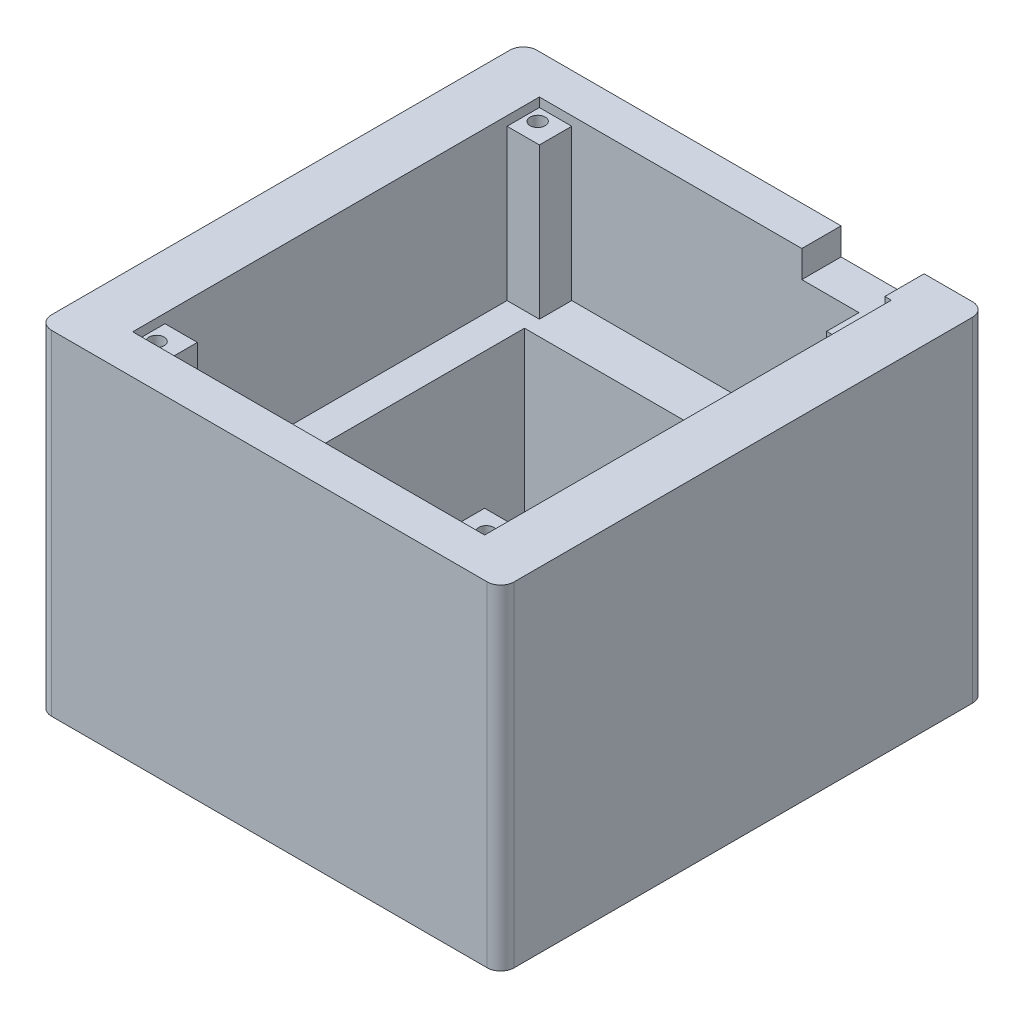
SolidWorks part; units mm, degrees
ref_plane "前视基准面" through (0, 0, 0) normal (0, 0, 1) x (1, 0, 0)
ref_plane "上视基准面" through (0, 0, 0) normal (0, 1, 0) x (1, 0, 0)
ref_plane "右视基准面" through (0, 0, 0) normal (1, 0, 0) x (0, 0, -1)
sketch "草图1" plane through (0, 0, 0) normal (0, 1, 0) x (1, 0, 0)
  line L1 (-4.635, 85.1381) -> (81.165, 85.1381)
  line L2 (-4.635, 85.1381) -> (-4.635, -4.8619)
  line L3 (-4.635, -4.8619) -> (81.165, -4.8619)
  line L4 (81.165, 85.1381) -> (81.165, -4.8619)
  line L7 (11.68, 11.2381) -> (64.85, 11.2381)
  line L8 (11.68, 11.2381) -> (11.68, 69.0381)
  line L9 (11.68, 69.0381) -> (64.85, 69.0381)
  line L10 (64.85, 11.2381) -> (64.85, 69.0381)
  circle A5 centre (1.745, 9.8381) radius 1.3379
  circle A6 centre (74.785, 9.8381) radius 1.3379
  circle A7 centre (74.785, 70.4381) radius 1.3379
  circle A8 centre (1.745, 70.4381) radius 1.3379
  point P10 (38.265, 85.1381)
  point P12 (38.265, 40.1381)
  point P13 (-4.635, 40.1381)
extrude "凸台-拉伸1" add sketch "草图1" along normal blind 20
sketch "草图3" plane through (0, 20, 0) normal (0, 1, 0) x (1, 0, 0)
  line L1 (-4.635, 85.1381) -> (81.165, 85.1381)
  line L2 (-4.635, 85.1381) -> (-4.635, -4.8619)
  line L3 (-4.635, -4.8619) -> (81.165, -4.8619)
  line L4 (81.165, 85.1381) -> (81.165, -4.8619)
  line L5 (11.68, 69.0381) -> (64.85, 69.0381)
  line L6 (11.68, 69.0381) -> (11.68, 11.2381)
  line L7 (11.68, 11.2381) -> (64.85, 11.2381)
  line L8 (64.85, 69.0381) -> (64.85, 11.2381)
extrude "凸台-拉伸2" add sketch "草图3" along normal blind 42
sketch "草图5" plane through (0, 62, 0) normal (0, 1, 0) x (1, 0, 0)
  line L0 (7.6859, 75.4766) -> (-4.635, 75.4766)
  line L1 (5.626, 77.8571) -> (70.904, 77.8571)
  line L2 (5.626, 77.8571) -> (5.626, 2.4191)
  line L3 (5.626, 2.4191) -> (70.904, 2.4191)
  line L4 (70.904, 77.8571) -> (70.904, 2.4191)
  line L5 (5.626, 77.8571) -> (70.904, 2.4191) construction
  line L6 (5.626, 2.4191) -> (70.904, 77.8571) construction
  line L7 (-4.635, 85.1381) -> (-4.635, -4.8619) construction
  line L8 (-4.635, 75.4766) -> (-4.635, 85.1381)
  circle A2 centre (7.6859, 75.4766) radius 1.4
  circle A3 centre (68.8441, 75.4766) radius 1.4
  circle A4 centre (68.8441, 4.7996) radius 1.4
  circle A5 centre (7.6859, 4.7996) radius 1.4
  point P0 (38.265, 40.1381)
  point P9 (0, 0)
  point P19 (38.265, 80.2762)
  point P21 (38.265, 40.1381)
  dimension "D1" = 2.0599
  dimension "D2" = 2.3805
extrude "切除-拉伸2" cut sketch "草图5" against normal blind 20 contours A2 | A5 | A4 | A3
extrude "切除-拉伸3" cut sketch "草图5<6>" against normal blind 1.7 contours L2 L3 L4 L1
sketch "草图5<6>" plane through (0, 62, 0) normal (0, 1, 0) x (1, 0, 0) same geometry as "草图5"
sketch "草图7" plane through (0, 60.3, 0) normal (0, 1, 0) x (1, 0, 0)
  line L0 (5.626, 71.8571) -> (11.626, 71.8571)
  line L1 (5.626, 77.8571) -> (5.626, 2.4191) construction
  line L2 (11.626, 71.8571) -> (11.626, 77.8571)
  line L3 (11.626, 77.8571) -> (64.9016, 77.8571)
  line L4 (64.9016, 77.8571) -> (64.9016, 71.8571)
  line L5 (64.9016, 71.8571) -> (70.9016, 71.8571)
  line L6 (70.9016, 71.8571) -> (70.904, 8.4191)
  line L7 (70.904, 77.8571) -> (70.904, 2.4191) construction
  line L8 (70.904, 8.4191) -> (64.904, 8.4191)
  line L9 (64.904, 8.4191) -> (64.904, 2.4191)
  line L10 (64.904, 2.4191) -> (11.626, 2.4191)
  line L11 (11.626, 2.4191) -> (11.626, 8.4191)
  line L12 (11.626, 8.4191) -> (5.626, 8.4191)
  line L13 (5.626, 8.4191) -> (5.626, 71.8571)
  point P16 (0, 0)
  point P17 (0, 0)
  point P18 (0, 0)
  point P19 (0, 0)
  point P20 (0, 0)
  dimension "D1" = 6
  dimension "D2" = 6
  dimension "D3" = 6
  dimension "D4" = 6
  dimension "D5" = 6
  dimension "D6" = 6
  dimension "D7" = 6
extrude "切除-拉伸4" cut sketch "草图7" against normal blind 28
sketch "草图8" plane through (0, 62, 0) normal (0, 1, 0) x (1, 0, 0)
  line L0 (69.697, 77.8571) -> (54.297, 77.8571)
  line L2 (81.165, 85.1381) -> (-4.635, 85.1381) construction
  line L4 (54.297, 77.8571) -> (54.297, 85.1381)
  line L5 (54.297, 85.1381) -> (69.697, 85.1381)
  line L6 (69.697, 77.8571) -> (69.697, 85.1381)
  dimension "D1" = 11.468
  dimension "D2" = 15.4
extrude "切除-拉伸5" cut sketch "草图8" against normal blind 5
fillet "圆角1" radius 2.5 1 edges at (-4.635, 31, -85.1381)
fillet "圆角2" radius 2.5 1 edges at (81.165, 31, -85.1381)
fillet "圆角3" radius 2.5 1 edges at (81.165, 31, 4.8619)
fillet "圆角4" radius 2.5 1 edges at (-4.635, 31, 4.8619)
sketch "草图10" plane through (0, 0, 0) normal (0, -1, 0) x (1, 0, 0)
sketch "草图11" plane through (0, 0, -77.8571) normal (0, 0, -1) x (-1, 0, 0)
  line L0 (-69.697, 57) -> (-64.9016, 57)
  line L1 (-64.9016, 57) -> (-64.9016, 60.3)
  line L2 (-64.9016, 60.3) -> (-69.697, 60.3)
  line L3 (-69.697, 60.3) -> (-69.697, 57)
extrude "切除-拉伸6" cut sketch "草图11" against normal blind 10
